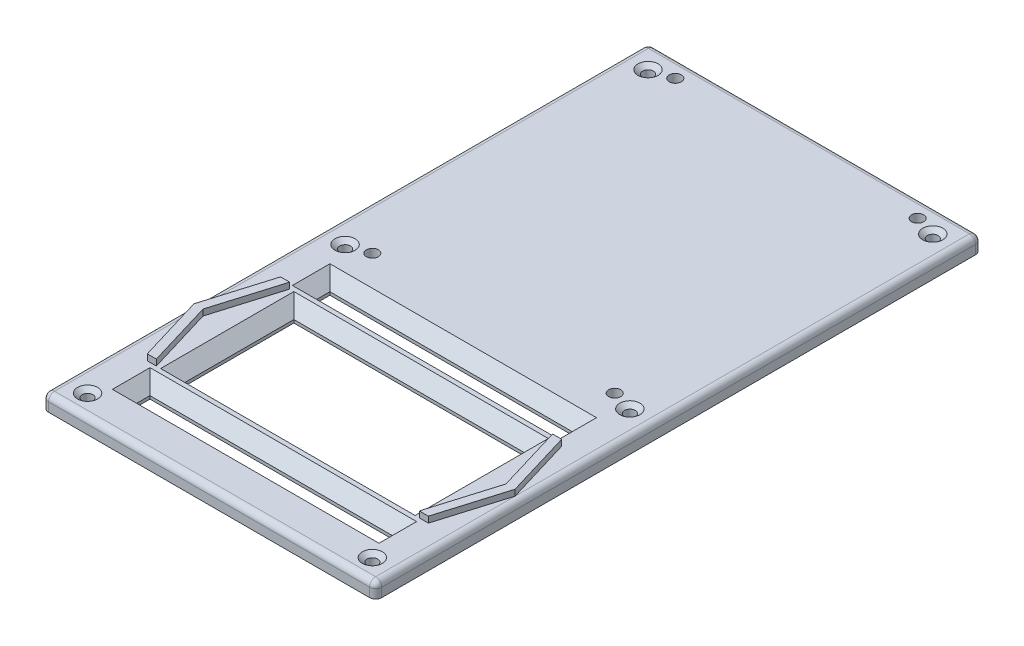
SolidWorks part; units mm, degrees
ref_plane "Front Plane" through (0, 0, 0) normal (0, 0, 1) x (1, 0, 0)
ref_plane "Top Plane" through (0, 0, 0) normal (0, 1, 0) x (1, 0, 0)
ref_plane "Right Plane" through (0, 0, 0) normal (1, 0, 0) x (0, 0, -1)
sketch "Sketch1" plane through (0, 0, 0) normal (0, 1, 0) x (1, 0, 0)
  line L1 (-69.85, -25.4) -> (69.85, -25.4)
  line L2 (-69.85, -25.4) -> (-69.85, 228.6)
  line L3 (-69.85, 228.6) -> (69.85, 228.6)
  line L4 (69.85, -25.4) -> (69.85, 228.6)
  line L5 (0, 228.6) -> (0, -25.4) construction
  line L6 (-69.85, 101.6) -> (69.85, 101.6) construction
  point P0 (0, 101.6)
  dimension "D1" = 254
  dimension "D2" = 139.7
  dimension "D3" = 101.6
extrude "Boss-Extrude1" add sketch "Sketch1" along normal blind 6.35
sketch "Sketch2" plane through (0, 6.35, 0) normal (0, 1, 0) x (1, 0, 0)
  line L0 (-69.85, -25.4) -> (69.85, -25.4) construction
  line L1 (-48.26, 12.7) -> (48.26, 12.7)
  line L2 (-48.26, 12.7) -> (-48.26, 58.42)
  line L3 (-48.26, 58.42) -> (48.26, 58.42)
  line L4 (48.26, 12.7) -> (48.26, 58.42)
  line L5 (0, 58.42) -> (0, 12.7) construction
  line L6 (-48.26, 35.56) -> (48.26, 35.56) construction
  point P0 (0, 35.56)
  dimension "D1" = 45.72
  dimension "D2" = 96.52
  dimension "D3" = 38.1
extrude "Main Hole" cut sketch "Sketch2" against normal through all
ref_plane "Plane1" through (0, 0, -35.56) normal (0, 0, 1) x (1, 0, 0)
sketch "Sketch3" plane through (0, 6.35, 0) normal (0, 1, 0) x (1, 0, 0)
  line L0 (48.26, 58.42) -> (-48.26, 58.42) construction
  line L1 (-50.8, 70.485) -> (50.8, 70.485)
  line L2 (-50.8, 70.485) -> (-50.8, 76.073)
  line L3 (-50.8, 76.073) -> (50.8, 76.073)
  line L4 (50.8, 70.485) -> (50.8, 76.073)
  point P4 (0, 70.485)
  dimension "D1" = 101.6
  dimension "D2" = 5.588
  dimension "D3" = 12.065
extrude "NeoPixel" cut sketch "Sketch3" against normal through all
mirror "Mirror2" about plane through (0, 0, -35.56) normal (0, 0, 1) of "NeoPixel"
sketch "Sketch5" plane through (0, 0, 0) normal (0, -1, 0) x (1, 0, 0)
  line L0 (69.85, -228.6) -> (-69.85, -228.6) construction
  line L1 (67.31, -226.06) -> (-67.31, -226.06)
  line L2 (67.31, -226.06) -> (67.31, 22.86)
  line L3 (67.31, 22.86) -> (-67.31, 22.86)
  line L4 (-67.31, -226.06) -> (-67.31, 22.86)
  line L5 (64.77, -223.52) -> (-64.77, -223.52)
  line L6 (64.77, -223.52) -> (64.77, 20.32)
  line L7 (64.77, 20.32) -> (-64.77, 20.32)
  line L8 (-64.77, -223.52) -> (-64.77, 20.32)
  line L9 (-69.85, -228.6) -> (-69.85, 25.4) construction
  line L10 (-69.85, 25.4) -> (69.85, 25.4) construction
  line L11 (69.85, 25.4) -> (69.85, -228.6) construction
  dimension "D1" = 2.54
  dimension "D2" = 2.54
  dimension "D3" = 2.54
  dimension "D4" = 2.54
  dimension "D5" = 2.54
  dimension "D6" = 2.54
  dimension "D7" = 2.54
  dimension "D8" = 2.54
extrude "Boss-Extrude2" [suppressed] add sketch "Sketch5" along normal blind 2.54 contours L4 L1 L2 L3 L5 L8 L7 L6
chamfer "Chamfer1" distance 5.08 angle 45 8 edges at (50.8, 6.35, 2.159) (0, 6.35, 4.953) (-50.8, 6.35, 2.159) (0, 6.35, -0.635) (-50.8, 6.35, -73.279) (0, 6.35, -70.485) (50.8, 6.35, -73.279) (0, 6.35, -76.073)
chamfer "Chamfer2" distance 5.08 angle 45 4 edges at (48.26, 6.35, -35.56) (0, 6.35, -12.7) (-48.26, 6.35, -35.56) (0, 6.35, -58.42)
sketch "Sketch6" plane through (0, 0, 0) normal (0, -1, 0) x (1, 0, 0)
  line L0 (0.6985, -35.56) -> (-0.6985, -35.56) construction
  line L1 (50.8, -10.16) -> (-50.8, -10.16)
  line L2 (50.8, -10.16) -> (50.8, -60.96)
  line L3 (50.8, -60.96) -> (-50.8, -60.96)
  line L4 (-50.8, -10.16) -> (-50.8, -60.96)
  line L5 (0, -60.96) -> (0, -10.16) construction
  line L6 (50.8, -35.56) -> (-50.8, -35.56) construction
  line L7 (0, -4.8895) -> (0, 4.8895) construction
  line L8 (6.35, -63.5) -> (6.35, -60.96)
  line L9 (53.34, -7.62) -> (-53.34, -7.62)
  line L10 (53.34, -7.62) -> (53.34, -63.5)
  line L11 (53.34, -63.5) -> (-53.34, -63.5)
  line L12 (-53.34, -7.62) -> (-53.34, -63.5)
  line L13 (0, -63.5) -> (0, -7.62) construction
  line L14 (53.34, -35.56) -> (-53.34, -35.56) construction
  line L31 (-6.35, -63.5) -> (-6.35, -60.96)
  line L32 (6.35, -62.23) -> (-6.35, -62.23) construction
  point P0 (0, -35.56)
  point P8 (0, -35.56)
  point P16 (0, -62.23)
  dimension "D1" = 2.54
  dimension "D2" = 2.54
  dimension "D3" = 50.8
  dimension "D4" = 101.6
  dimension "D5" = 12.7
extrude "Boss-Extrude3" [suppressed] add sketch "Sketch6" along normal blind 4.064 contours L9 L12 L11 L10 L4 L1 L2 L3
sketch "Sketch7" plane through (0, 6.35, 0) normal (0, 1, 0) x (1, 0, 0)
  line L0 (-50.8, 93.853) -> (50.8, 93.853) construction
  line L1 (0, -3.4925) -> (0, 3.4925) construction
  line L2 (-55.88, 81.153) -> (55.88, 81.153) construction
  circle A0 centre (50.8, 93.853) radius 2.54
  circle A1 centre (-50.8, 93.853) radius 2.54
  circle A2 centre (-50.8, 220.853) radius 2.54
  circle A3 centre (50.8, 220.853) radius 2.54
  point P4 (0, 93.853)
  dimension "D1" = 5.08
  dimension "D3" = 12.7
  dimension "D5" = 127
  dimension "D2" = 101.6
  dimension "D4" = 2
extrude "Cut-Extrude1" cut sketch "Sketch7" against normal up to next
sketch "Sketch8" plane through (0, 6.35, 0) normal (0, 1, 0) x (1, 0, 0)
  line L0 (58.928, 63.5) -> (67.31, 35.56)
  line L1 (67.31, 35.56) -> (58.928, 7.62)
  line L2 (58.928, 7.62) -> (55.118, 7.62)
  line L3 (55.118, 7.62) -> (63.5, 35.56)
  line L4 (63.5, 35.56) -> (55.118, 63.5)
  line L5 (55.118, 63.5) -> (58.928, 63.5)
  line L6 (63.5, 35.56) -> (67.31, 35.56) construction
  line L7 (-53.34, 63.5) -> (53.34, 63.5) construction
  line L8 (-3.4925, 35.56) -> (3.4925, 35.56) construction
  line L9 (53.34, 7.62) -> (-53.34, 7.62) construction
  dimension "D1" = 3.81
  dimension "D2" = 8.382
  dimension "D3" = 1.778
extrude "Boss-Extrude4" add sketch "Sketch8" along normal blind 2.54
mirror "Mirror3" about plane through (0, 0, 0) normal (1, 0, 0) of "Boss-Extrude4"
hole_wizard "Front-Back Mounting HOles" positions "Sketch9" profile "Sketch10" countersink size "#8" standard "ANSI Inch" end condition through all
sketch "Sketch9" plane through (0, 6.35, 0) normal (0, 1, 0) x (1, 0, 0)
  line L0 (69.85, -25.4) -> (69.85, 228.6) construction
  line L1 (-69.85, 228.6) -> (-69.85, -25.4) construction
  line L2 (69.85, 228.6) -> (-69.85, 228.6) construction
  point P0 (59.69, 218.313)
  point P2 (-59.69, 218.313)
  point P4 (-59.69, 91.313)
  point P6 (59.69, 91.313)
  point P8 (59.69, -16.637)
  point P10 (-59.69, -16.637)
  dimension "D5" = 10.287
  dimension "D1" = 10.16
  dimension "D2" = 10.16
  dimension "D3" = 107.95
  dimension "D4" = 127
sketch "Sketch10" plane through (59.69, 6.35, -218.313) normal (1, 0, 0) x (0, 0, 1)
  line L0 (0, 0) -> (0, 6.35)
  line L1 (0, 6.35) -> (2.2479, 6.35)
  line L2 (2.2479, 6.35) -> (2.2479, 1.6518)
  line L3 (2.2479, 1.6518) -> (4.2164, 0)
  line L5 (4.2164, 0) -> (0, 0)
  line L6 (-2.2479, 1.6518) -> (-4.2164, 0) construction
  line L11 (0, -6.35) -> (0, 107.95) construction
  dimension "Thru Hole Dia." = 4.4958
  dimension "Thru Hole Depth" = 6.35
  dimension "Near C'Sink Dia." = 8.4328
  dimension "Near C'Sink Angle" = 100
fillet "Corner Fillet" radius 2.54 4 edges at (-69.85, 3.175, -228.6) (69.85, 3.175, -228.6) (-69.85, 3.175, 25.4) (69.85, 3.175, 25.4)
fillet "Fillet2" radius 2.54 8 edges at (-69.1061, 6.35, -227.8561) (0, 6.35, -228.6) (69.1061, 6.35, -227.8561) (69.85, 6.35, -101.6) (69.1061, 6.35, 24.6561) (0, 6.35, 25.4) (-69.1061, 6.35, 24.6561) (-69.85, 6.35, -101.6)
equation "\"D1@Sketch2\"=1.8in"
equation "\"D2@Sketch2\"=3.8in"
